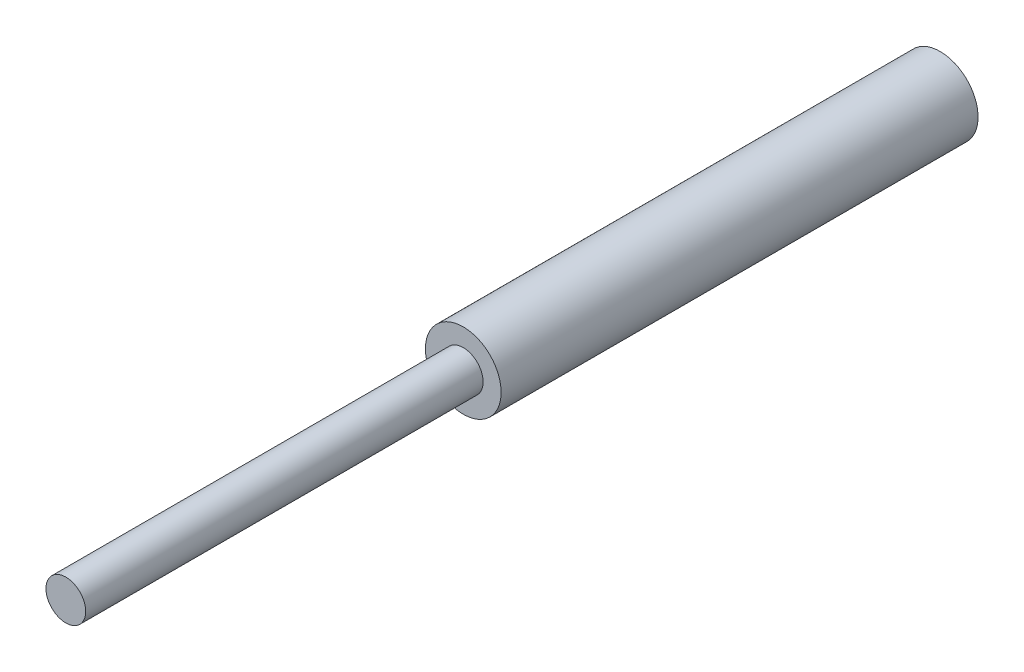
SolidWorks part; units mm, degrees
ref_plane "Front Plane" through (0, 0, 0) normal (0, 0, 1) x (1, 0, 0)
ref_plane "Top Plane" through (0, 0, 0) normal (0, 1, 0) x (1, 0, 0)
ref_plane "Right Plane" through (0, 0, 0) normal (1, 0, 0) x (0, 0, -1)
sketch "Sketch2" plane through (0, 0, 0) normal (0, 0, 1) x (1, 0, 0)
  circle A0 centre (0, 0) radius 2.5
  dimension "D1" = 5
extrude "Boss-Extrude1" add sketch "Sketch2" along normal blind 50
sketch "Sketch3" plane through (0, 0, 0) normal (0, 0, -1) x (-1, 0, 0)
  circle A0 centre (0, 0) radius 4.7625
  dimension "D1" = 9.525
extrude "Boss-Extrude2" add sketch "Sketch3" along normal blind 60
ref_axis "Axis1" through (0, 0, -66.8229) along (0, 0, 1)
